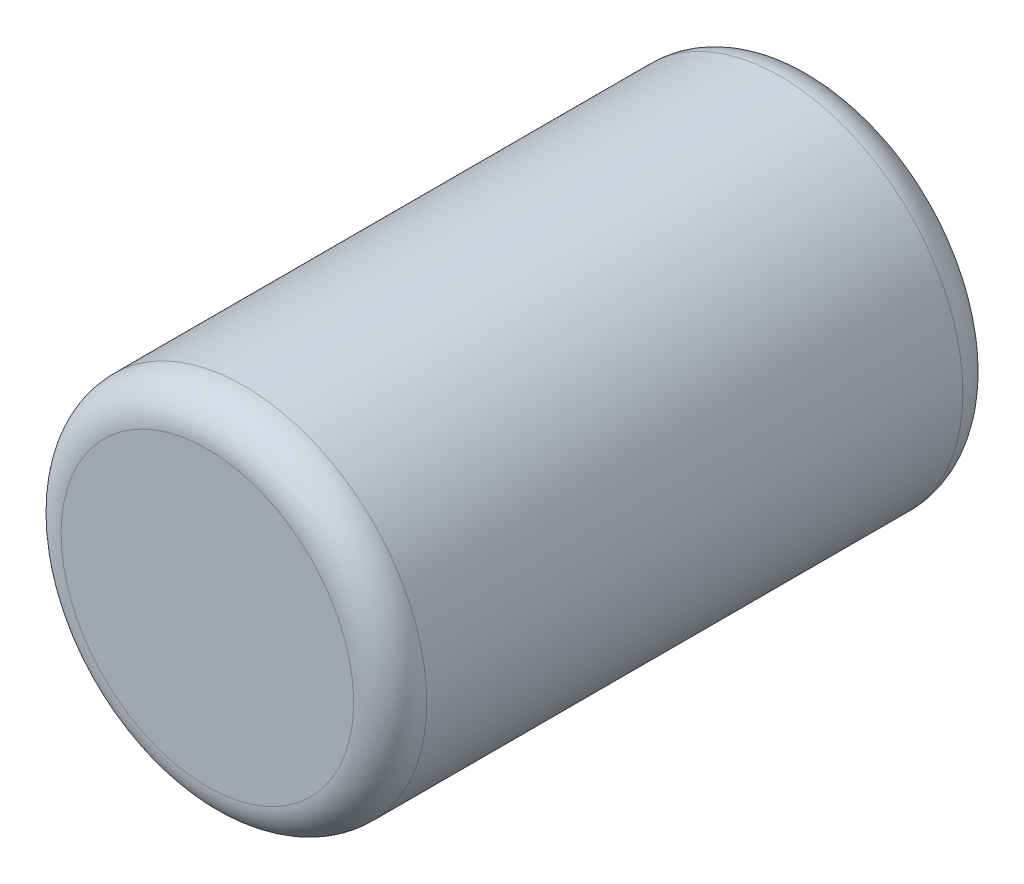
SolidWorks part; units mm, degrees
ref_plane "Front" through (0, 0, 0) normal (0, 0, 1) x (1, 0, 0)
ref_plane "Top" through (0, 0, 0) normal (0, 1, 0) x (1, 0, 0)
ref_plane "Right" through (0, 0, 0) normal (1, 0, 0) x (0, 0, -1)
sketch "Эскиз2" plane through (0, 0, 0) normal (1, 0, 0) x (0, 0, -1)
  line L0 (0, 0) -> (-9.8044, 0) construction
  line L1 (0, 0) -> (-5, 0)
  line L2 (0, 0) -> (0, -1.2)
  line L3 (-0.3, -1.5) -> (-4.7, -1.5)
  line L4 (-5, -1.2) -> (-5, 0)
  arc A0 (0, -1.2) -> (-0.3, -1.5) centre (-0.3, -1.2) cw
  arc A1 (-4.7, -1.5) -> (-5, -1.2) centre (-4.7, -1.2) cw
  dimension "D1" = 3
  dimension "D3" = 0.3
  dimension "D2" = 5
revolve "Повернуть1" add sketch "Эскиз2" angle 360 about L0
